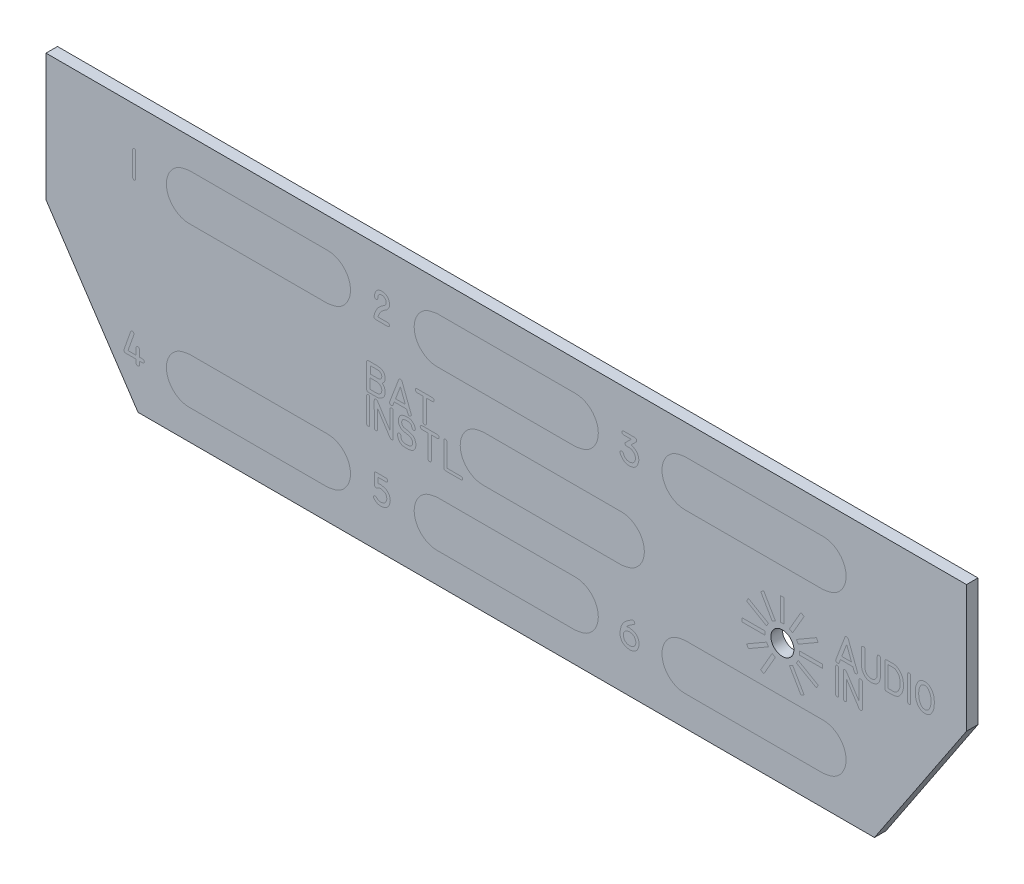
SolidWorks part; units mm, degrees
ref_plane "Front Plane" through (0, 0, 0) normal (0, 0, 1) x (1, 0, 0)
ref_plane "Top Plane" through (0, 0, 0) normal (0, 1, 0) x (1, 0, 0)
ref_plane "Right Plane" through (0, 0, 0) normal (1, 0, 0) x (0, 0, -1)
sketch "Sketch1" plane through (0, 0, 0) normal (0, 0, 1) x (1, 0, 0)
  line L12 (22.225, 2.286) -> (123.825, 2.286)
  line L13 (123.825, 2.286) -> (136.525, 21.336)
  line L14 (136.525, 21.336) -> (136.525, 38.862)
  line L15 (136.525, 38.862) -> (9.525, 38.862)
  line L16 (9.525, 38.862) -> (9.525, 21.336)
  line L17 (9.525, 21.336) -> (22.225, 2.286)
extrude "Boss-Extrude1" add sketch "Sketch1" along normal blind 1.5875
sketch "Sketch2" plane through (0, 0, 1.5875) normal (0, 0, 1) x (1, 0, 0)
  line L0 (73.025, 38.862) -> (73.025, 31.5468) construction
  line L1 (136.525, 38.862) -> (9.525, 38.862) construction
  line L2 (73.025, 31.5468) -> (73.025, 24.2316) construction
  line L3 (73.025, 24.2316) -> (73.025, 16.9164) construction
  line L4 (73.025, 16.9164) -> (73.025, 9.6012) construction
  line L5 (73.025, 9.6012) -> (73.025, 2.286) construction
  line L6 (22.225, 2.286) -> (123.825, 2.286) construction
  line L7 (63.5, 9.6012) -> (82.55, 9.6012) construction
  line L8 (63.5, 12.7762) -> (82.55, 12.7762)
  line L9 (63.5, 6.4262) -> (82.55, 6.4262)
  line L10 (63.5, 31.5468) -> (82.55, 31.5468) construction
  line L11 (63.5, 34.7218) -> (82.55, 34.7218)
  line L12 (63.5, 28.3718) -> (82.55, 28.3718)
  line L13 (60.325, 9.6012) -> (17.3482, 9.6012) construction
  line L14 (9.525, 21.336) -> (22.225, 2.286) construction
  line L15 (29.3116, 9.6012) -> (48.3616, 9.6012) construction
  line L16 (29.3116, 12.7762) -> (48.3616, 12.7762)
  line L17 (29.3116, 6.4262) -> (48.3616, 6.4262)
  line L18 (60.325, 31.5468) -> (9.525, 31.5468) construction
  line L19 (9.525, 38.862) -> (9.525, 21.336) construction
  line L20 (29.3116, 31.5468) -> (48.3616, 31.5468) construction
  line L21 (29.3116, 34.7218) -> (48.3616, 34.7218)
  line L22 (29.3116, 28.3718) -> (48.3616, 28.3718)
  line L23 (73.025, 20.574) -> (79.375, 20.574) construction
  line L24 (88.9, 20.574) -> (69.85, 20.574) construction
  line L25 (88.9, 17.399) -> (69.85, 17.399)
  line L26 (88.9, 23.749) -> (69.85, 23.749)
  line L27 (116.7384, 31.5468) -> (97.6884, 31.5468) construction
  line L28 (116.7384, 34.7218) -> (97.6884, 34.7218)
  line L29 (116.7384, 28.3718) -> (97.6884, 28.3718)
  line L30 (116.7384, 9.6012) -> (97.6884, 9.6012) construction
  line L31 (116.7384, 12.7762) -> (97.6884, 12.7762)
  line L32 (116.7384, 6.4262) -> (97.6884, 6.4262)
  line L33 (21.7424, 31.5468) -> (21.7424, 29.7688) construction
  line L34 (19.3612, 29.7688) -> (24.1237, 29.7688) construction
  line L35 (48.3616, 28.3718) -> (63.5, 28.3718) construction
  line L36 (55.9308, 28.3718) -> (55.9308, 29.7688) construction
  line L37 (53.5496, 29.7688) -> (58.3121, 29.7688) construction
  line L38 (82.55, 28.3718) -> (97.6884, 28.3718) construction
  line L39 (90.1192, 28.3718) -> (90.1192, 29.7688) construction
  line L40 (87.738, 29.7688) -> (92.5005, 29.7688) construction
  line L41 (19.3612, 7.8232) -> (24.1237, 7.8232) construction
  line L42 (53.5496, 7.8232) -> (58.3121, 7.8232) construction
  line L43 (92.5005, 7.8232) -> (87.738, 7.8232) construction
  line L44 (53.5496, 22.352) -> (53.5496, 16.51) construction
  line L45 (53.5496, 20.574) -> (65.0729, 20.574) construction
  line L46 (53.5496, 16.51) -> (65.0729, 16.51) construction
  line L47 (111.125, 21.5447) -> (111.125, 24.7197) construction
  line L48 (111.379, 21.5447) -> (111.379, 24.7197)
  line L49 (110.871, 21.5447) -> (110.871, 24.7197)
  line L50 (111.379, 21.5447) -> (110.871, 21.5447)
  line L51 (111.379, 24.7197) -> (110.871, 24.7197)
  line L52 (112.5356, 21.0986) -> (114.1231, 23.8483)
  line L53 (112.0957, 21.3526) -> (113.6832, 24.1023)
  line L54 (112.5356, 21.0986) -> (112.0957, 21.3526)
  line L55 (114.1231, 23.8483) -> (113.6832, 24.1023)
  line L56 (113.3142, 20.1341) -> (116.0639, 21.7216)
  line L57 (113.0602, 20.574) -> (115.8099, 22.1615)
  line L58 (113.3142, 20.1341) -> (113.0602, 20.574)
  line L59 (116.0639, 21.7216) -> (115.8099, 22.1615)
  line L60 (113.5063, 18.9094) -> (116.6813, 18.9094)
  line L61 (113.5063, 19.4174) -> (116.6813, 19.4174)
  line L62 (113.5063, 18.9094) -> (113.5063, 19.4174)
  line L63 (116.6813, 18.9094) -> (116.6813, 19.4174)
  line L64 (113.0602, 17.7528) -> (115.8099, 16.1653)
  line L65 (113.3142, 18.1928) -> (116.0639, 16.6053)
  line L66 (113.0602, 17.7528) -> (113.3142, 18.1928)
  line L67 (115.8099, 16.1653) -> (116.0639, 16.6053)
  line L68 (112.0957, 16.9742) -> (113.6832, 14.2246)
  line L69 (112.5356, 17.2282) -> (114.1231, 14.4786)
  line L70 (112.0957, 16.9742) -> (112.5356, 17.2282)
  line L71 (113.6832, 14.2246) -> (114.1231, 14.4786)
  line L72 (110.871, 16.7822) -> (110.871, 13.6072) [skipped]
  line L73 (111.379, 16.7822) -> (111.379, 13.6072) [skipped]
  line L74 (110.871, 16.7822) -> (111.379, 16.7822) [skipped]
  line L75 (110.871, 13.6072) -> (111.379, 13.6072) [skipped]
  line L76 (109.7144, 17.2282) -> (108.1269, 14.4786)
  line L77 (110.1543, 16.9742) -> (108.5668, 14.2246)
  line L78 (109.7144, 17.2282) -> (110.1543, 16.9742)
  line L79 (108.1269, 14.4786) -> (108.5668, 14.2246)
  line L80 (108.9358, 18.1928) -> (106.1861, 16.6053)
  line L81 (109.1898, 17.7528) -> (106.4401, 16.1653)
  line L82 (108.9358, 18.1928) -> (109.1898, 17.7528)
  line L83 (106.1861, 16.6053) -> (106.4401, 16.1653)
  line L84 (108.7438, 19.4174) -> (105.5688, 19.4174)
  line L85 (108.7438, 18.9094) -> (105.5688, 18.9094)
  line L86 (108.7438, 19.4174) -> (108.7438, 18.9094)
  line L87 (105.5688, 19.4174) -> (105.5688, 18.9094)
  line L88 (109.1898, 20.574) -> (106.4401, 22.1615)
  line L89 (108.9358, 20.1341) -> (106.1861, 21.7216)
  line L90 (109.1898, 20.574) -> (108.9358, 20.1341)
  line L91 (106.4401, 22.1615) -> (106.1861, 21.7216)
  line L92 (110.1543, 21.3526) -> (108.5668, 24.1023)
  line L93 (109.7144, 21.0986) -> (108.1269, 23.8483)
  line L94 (110.1543, 21.3526) -> (109.7144, 21.0986)
  line L95 (108.5668, 24.1023) -> (108.1269, 23.8483)
  line L96 (118.2688, 21.8168) -> (118.2688, 16.51) construction
  line L97 (118.2688, 19.1634) -> (116.6813, 19.1634) construction
  line L98 (118.2688, 16.51) -> (131.5548, 16.51) construction
  line L99 (118.2688, 20.574) -> (133.3905, 20.574) construction
  arc A0 (63.5, 12.7762) -> (63.5, 6.4262) centre (63.5, 9.6012) ccw
  arc A1 (82.55, 6.4262) -> (82.55, 12.7762) centre (82.55, 9.6012) ccw
  arc A2 (63.5, 34.7218) -> (63.5, 28.3718) centre (63.5, 31.5468) ccw
  arc A3 (82.55, 28.3718) -> (82.55, 34.7218) centre (82.55, 31.5468) ccw
  arc A4 (29.3116, 12.7762) -> (29.3116, 6.4262) centre (29.3116, 9.6012) ccw
  arc A5 (48.3616, 6.4262) -> (48.3616, 12.7762) centre (48.3616, 9.6012) ccw
  arc A6 (29.3116, 34.7218) -> (29.3116, 28.3718) centre (29.3116, 31.5468) ccw
  arc A7 (48.3616, 28.3718) -> (48.3616, 34.7218) centre (48.3616, 31.5468) ccw
  arc A8 (88.9, 17.399) -> (88.9, 23.749) centre (88.9, 20.574) ccw
  arc A9 (69.85, 23.749) -> (69.85, 17.399) centre (69.85, 20.574) ccw
  arc A10 (116.7384, 34.7218) -> (116.7384, 28.3718) centre (116.7384, 31.5468) cw
  arc A11 (97.6884, 28.3718) -> (97.6884, 34.7218) centre (97.6884, 31.5468) cw
  arc A12 (116.7384, 12.7762) -> (116.7384, 6.4262) centre (116.7384, 9.6012) cw
  arc A13 (97.6884, 6.4262) -> (97.6884, 12.7762) centre (97.6884, 9.6012) cw
  circle A14 centre (111.125, 19.1634) radius 2.3813 construction
  text T0 "2"
  text T1 "1"
  text T2 "3"
  text T3 "4"
  text T4 "5"
  text T5 "6"
  text T6 "BAT"
  text T7 "INSTL"
  text T8 "AUDIO"
  text T9 "IN"
  point P12 (73.025, 9.6012)
  point P19 (73.025, 31.5468)
  point P30 (38.8366, 9.6012)
  point P41 (38.8366, 31.5468)
  point P50 (79.375, 20.574)
  point P57 (107.2134, 31.5468)
  point P64 (107.2134, 9.6012)
  point P74 (21.7424, 29.7688)
  point P80 (55.9308, 29.7688)
  point P89 (90.1192, 29.7688)
  point P157 (111.125, 19.1634)
  dimension "D11" = 4.7625
  dimension "D1" = 19.05
  dimension "D2" = 6.35
  dimension "D3" = 6.35
  dimension "D4" = 4.7625
  dimension "D5" = 7.5692
  dimension "D6" = 1.778
  dimension "D7" = 7.5692
  dimension "D8" = 1.778
  dimension "D9" = 4.064
  dimension "D10" = 1.778
  dimension "D16" = 1.5875
  dimension "D12" = 22.225
  dimension "D17" = 3.175
  dimension "D13" = 0.254
  dimension "D14" = 0.254
  dimension "D15" = 12
wrap "Wrap3" sketch "Sketch2" wrap type scribe source sketch "Sketch2"
sketch "Sketch3" plane through (0, 0, 1.5875) normal (0, 0, 1) x (1, 0, 0)
  line L0 (112.3156, 17.1012) -> (109.9344, 21.2256) construction
  line L1 (112.0957, 16.9742) -> (112.5356, 17.2282) construction
  line L2 (110.1543, 21.3526) -> (109.7144, 21.0986) construction
  circle A0 centre (111.125, 19.1634) radius 1.5875
  dimension "D1" = 3.175
extrude "Cut-Extrude1" cut sketch "Sketch3" against normal up to next
equation "\"D5@Sketch2\"=\"D7@Sketch2\""
equation "\"D8@Sketch2\"=\"D6@Sketch2\""
